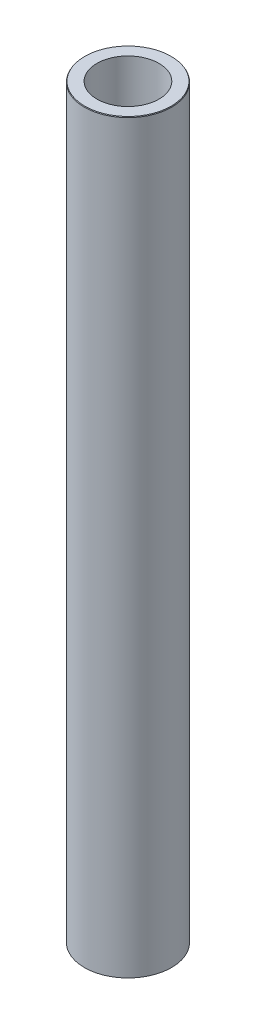
SolidWorks part; units mm, degrees
ref_plane "Front Plane" through (0, 0, 0) normal (0, 0, 1) x (1, 0, 0)
ref_plane "Top Plane" through (0, 0, 0) normal (0, 1, 0) x (1, 0, 0)
ref_plane "Right Plane" through (0, 0, 0) normal (1, 0, 0) x (0, 0, -1)
sketch "Sketch1" plane through (0, 0, 0) normal (0, 1, 0) x (1, 0, 0)
  circle A0 centre (0, 0) radius 15
  dimension "SHAFT_OD" = 30
extrude "Boss-Extrude1" add sketch "Sketch1" along normal blind 256.8321
sketch "Sketch2" plane through (0, 0, 0) normal (0, 1, 0) x (1, 0, 0)
  circle A0 centre (0, 0) radius 10.6763
  dimension "BORE_D" = 21.3525
extrude "Cut-Extrude1" cut sketch "Sketch2" along normal through all
chamfer "Chamfer1" distance 0.2467 angle 30 2 edges at (0, 256.8321, 15) (0, 0, 15) first distance on face at (0, 256.8321, 15) first distance on face at (0, 0, 10.6763)
